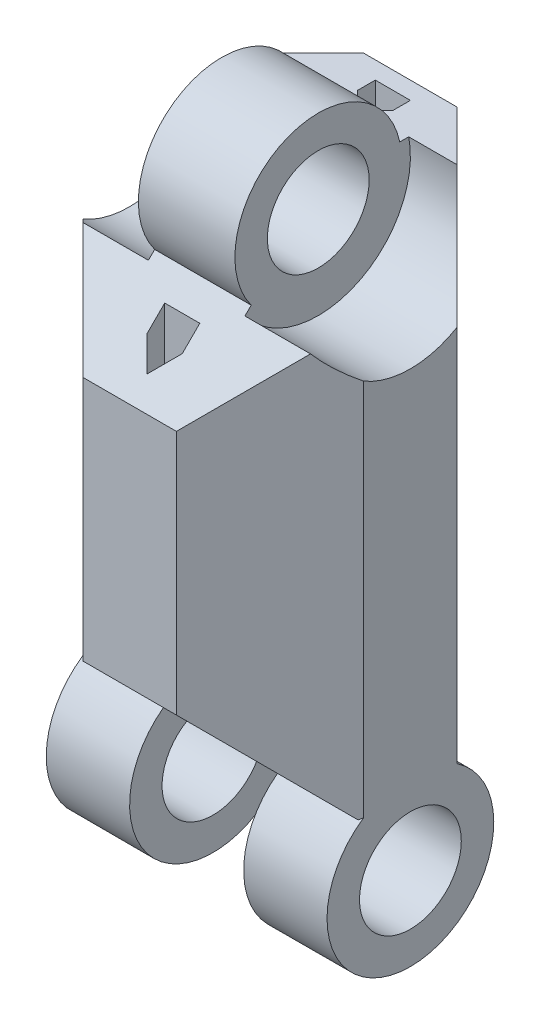
SolidWorks part; units mm, degrees
ref_plane "Front Plane" through (0, 0, 0) normal (0, 0, 1) x (1, 0, 0)
ref_plane "Top Plane" through (0, 0, 0) normal (0, 1, 0) x (1, 0, 0)
ref_plane "Right Plane" through (0, 0, 0) normal (1, 0, 0) x (0, 0, -1)
sketch "Sketch1" plane through (0, 0, 0) normal (0, 1, 0) x (1, 0, 0)
  line L0 (-1.3333, -4) -> (1.3333, -4)
  line L1 (1.3333, -4) -> (4, -1.3333)
  line L2 (4, -1.3333) -> (4, 1.3333)
  line L3 (4, 1.3333) -> (1.3333, 4)
  line L4 (1.3333, 4) -> (-1.3333, 4)
  line L5 (-1.3333, 4) -> (-4, 1.3333)
  line L6 (-4, 1.3333) -> (-4, -1.3333)
  line L7 (-4, -1.3333) -> (-1.3333, -4)
  point P16 (4, 0)
  point P19 (0, -4)
  dimension "D1" = 135
  dimension "D2" = 8
  dimension "D3" = 8
  dimension "D4" = 2.6667
extrude "Boss-Extrude1" add sketch "Sketch1" along normal blind 15
sketch "Sketch2" plane through (0, 0, 0) normal (1, 0, 0) x (0, 0, -1)
  line L0 (0, 15) -> (-4, 15)
  line L1 (-1.3333, 15) -> (1.3333, 15) construction
  line L2 (-4, 15) -> (-4, 11)
  line L3 (-4, 15) -> (-4, 0) construction
  line L4 (-4, 11) -> (0, 15)
  line L5 (0, 0) -> (-4, 0)
  line L6 (-1.3333, 0) -> (1.3333, 0) construction
  line L7 (-4, 0) -> (-4, 4)
  line L8 (-4, 4) -> (0, 0)
  dimension "D1" = 45
  dimension "D2" = 45
extrude "Cut-Extrude1" cut sketch "Sketch2" against normal through all both and the other way through all contours L4 L0 L2 | L8 L5 L7
sketch "Sketch3" plane through (0, 0, 0) normal (0, 1, 0) x (1, 0, 0)
  line L0 (0, -3.5) -> (-0.5, -3)
  line L1 (-0.5, -3) -> (-0.5, -2.5)
  line L2 (-0.5, -2.5) -> (0.5, -2.5)
  line L3 (0.5, -2.5) -> (0.5, -3)
  line L4 (0.5, -3) -> (0, -3.5)
  line L5 (-1.3333, -4) -> (1.3333, -4) construction
  line L6 (0.5, 3.5) -> (0.5, 3)
  line L7 (-0.5, 3.5) -> (0.5, 3.5)
  line L8 (-0.5, 3) -> (-0.5, 3.5)
  line L9 (0, 2.5) -> (-0.5, 3)
  line L10 (0.5, 3) -> (0, 2.5)
  line L11 (1.3333, 4) -> (-1.3333, 4) construction
  point P6 (0, -2.5)
  point P13 (0, -4)
  dimension "D1" = 1
  dimension "D2" = 0.5
  dimension "D3" = 0.5
  dimension "D4" = 0.5
  dimension "D5" = 0.5
  dimension "D6" = 2
  dimension "D7" = 0.5
extrude "Cut-Extrude2" cut sketch "Sketch3" along normal through all
sketch "Sketch4" plane through (0, 0, 0) normal (1, 0, 0) x (0, 0, -1)
  circle A0 centre (0, 14.5) radius 2.375
  dimension "D2" = 4.75
  dimension "D1" = 0.5
extrude "Boss-Extrude2" add sketch "Sketch4" along normal mid plane 2.75
sketch "Sketch5" plane through (1.375, 0, 0) normal (1, 0, 0) x (0, 0, -1)
  circle A0 centre (0, 14.5) radius 2.625
  dimension "D1" = 5.25
extrude "Cut-Extrude3" cut sketch "Sketch5" along normal through all
mirror "Mirror1" about plane through (0, 0, 0) normal (1, 0, 0) of "Cut-Extrude3"
sketch "Sketch6" plane through (0, 0, 0) normal (1, 0, 0) x (0, 0, -1)
  circle A0 centre (0, -0.5) radius 2.625
  dimension "D2" = 5.25
  dimension "D1" = 0.5
extrude "Cut-Extrude4" cut sketch "Sketch6" against normal mid plane 3.25
sketch "Sketch7" plane through (-1.625, 0, 0) normal (1, 0, 0) x (0, 0, -1)
  circle A0 centre (0, -0.5) radius 2.375
  dimension "D2" = 4.75
  dimension "D1" = 0.5
extrude "Boss-Extrude3" add sketch "Sketch7" against normal up to surface (2.375 mm away) up to face at (-4, 5.0894, 0)
sketch "Sketch8" plane through (1.625, 0, 0) normal (-1, 0, 0) x (0, 0, 1)
  circle A0 centre (0, -0.5) radius 2.375
  dimension "D2" = 4.75
  dimension "D1" = 0.5
extrude "Boss-Extrude4" add sketch "Sketch8" against normal up to surface (2.375 mm away) up to face at (4, 5.0894, 0)
sketch "Sketch10" plane through (1.375, 0, 0) normal (1, 0, 0) x (0, 0, -1)
  circle A0 centre (0, 14.5) radius 1.45
  dimension "D1" = 2.9
extrude "Cut-Extrude5" cut sketch "Sketch10" against normal through all both and the other way through all
sketch "Sketch11" plane through (4, 0, 0) normal (1, 0, 0) x (0, 0, -1)
  circle A0 centre (0, -0.5) radius 1.45
  dimension "D1" = 2.9
extrude "Cut-Extrude6" cut sketch "Sketch11" against normal through all both and the other way through all
